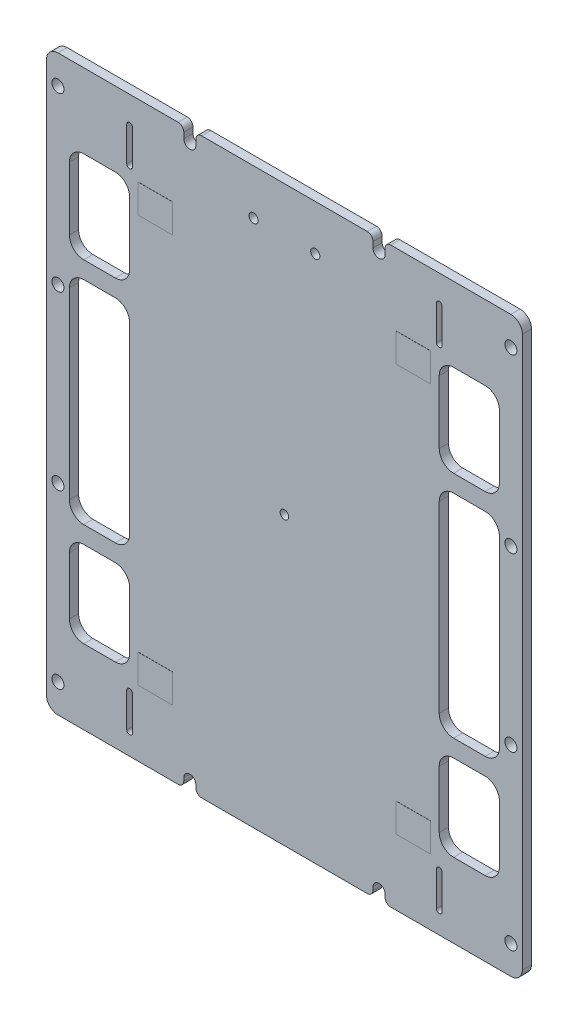
SolidWorks part; units mm, degrees
material "FR4_stuffedProtoboard"
ref_plane "Front Plane" through (0, 0, 0) normal (0, 0, 1) x (1, 0, 0)
ref_plane "Top Plane" through (0, 0, 0) normal (0, 1, 0) x (1, 0, 0)
ref_plane "Right Plane" through (0, 0, 0) normal (1, 0, 0) x (0, 0, -1)
sketch "Sketch1" plane through (0, 0, 0) normal (0, 0, 1) x (1, 0, 0)
  line L1 (-39.5, -50) -> (39.5, -50)
  line L2 (-41.5, -48) -> (-41.5, 48)
  line L3 (-39.5, 50) -> (39.5, 50)
  line L4 (41.5, -48) -> (41.5, 48)
  line L5 (-41.5, -50) -> (41.5, 50) construction
  line L6 (-41.5, 50) -> (41.5, -50) construction
  arc A0 (-39.5, -50) -> (-41.5, -48) centre (-39.5, -48) cw
  arc A1 (39.5, -50) -> (41.5, -48) centre (39.5, -48) ccw
  arc A2 (39.5, 50) -> (41.5, 48) centre (39.5, 48) cw
  arc A3 (-41.5, 48) -> (-39.5, 50) centre (-39.5, 48) cw
  point P0 (0, 0)
  dimension "D3" = 2
  dimension "D1" = 100
  dimension "D2" = 83
extrude "boardOutline" add sketch "Sketch1" along normal blind 1.6
sketch "Sketch2" plane through (0, 0, 1.6) normal (0, 0, 1) x (1, 0, 0)
  line L0 (39.5, 50) -> (-39.5, 50) construction
  line L1 (-41.5, 48) -> (-41.5, -48) construction
  line L2 (-5.385, 42.1) -> (5.385, 42.1) construction
  line L3 (-38, 44.2) -> (-38, 4.2) construction
  line L4 (0, 42.1) -> (0, 50) construction
  circle A0 centre (0, 0) radius 0.75
  circle A1 centre (-38, 44.2) radius 1.05 construction
  circle A2 centre (37.5, 44.2) radius 1.05 construction
  circle A3 centre (37.5, 4.2) radius 1.05 construction
  circle A4 centre (37.5, -35.8) radius 1.05 construction
  circle A5 centre (-38, 4.2) radius 1.05 construction
  circle A6 centre (-38, -35.8) radius 1.05 construction
  circle A7 centre (-5.385, 42.1) radius 0.8
  circle A8 centre (5.385, 42.1) radius 0.8
  dimension "D1" = 1.5
  dimension "D2" = 2.1
  dimension "D9" = 10.77
  dimension "D7" = 1.6
  dimension "D11" = 7.9
  dimension "D3" = 5.8
  dimension "D4" = 3.5
  dimension "D8" = 40
  dimension "D10" = 37.5
  dimension "D5" = 2
  dimension "D6" = 3
extrude "componentHoles" cut sketch "Sketch2" against normal through all
sketch "Sketch4" plane through (0, 0, 1.6) normal (0, 0, 1) x (1, 0, 0)
  line L0 (-27, 39.25) -> (-27, 45.25) construction
  line L1 (-27.5, 39.25) -> (-27.5, 45.25)
  line L2 (-26.5, 39.25) -> (-26.5, 45.25)
  line L3 (39.5, 50) -> (-39.5, 50) construction
  line L4 (-41.5, 48) -> (-41.5, -48) construction
  line L5 (27, 39.25) -> (27, 45.25) construction
  line L6 (26.5, 39.25) -> (26.5, 45.25)
  line L7 (27.5, 39.25) -> (27.5, 45.25)
  line L8 (27, -46.25) -> (27, -40.25) construction
  line L9 (26.5, -46.25) -> (26.5, -40.25)
  line L10 (27.5, -46.25) -> (27.5, -40.25)
  line L11 (-27, -46.25) -> (-27, -40.25) construction
  line L12 (-27.5, -46.25) -> (-27.5, -40.25)
  line L13 (-26.5, -46.25) -> (-26.5, -40.25)
  line L14 (-27, 39.25) -> (27, 39.25) construction
  line L15 (0, 39.25) -> (0, 50) construction
  arc A0 (-27.5, 39.25) -> (-26.5, 39.25) centre (-27, 39.25) ccw
  arc A1 (-26.5, 45.25) -> (-27.5, 45.25) centre (-27, 45.25) ccw
  arc A2 (26.5, 39.25) -> (27.5, 39.25) centre (27, 39.25) ccw
  arc A3 (27.5, 45.25) -> (26.5, 45.25) centre (27, 45.25) ccw
  arc A4 (26.5, -46.25) -> (27.5, -46.25) centre (27, -46.25) ccw
  arc A5 (27.5, -40.25) -> (26.5, -40.25) centre (27, -40.25) ccw
  arc A6 (-27.5, -46.25) -> (-26.5, -46.25) centre (-27, -46.25) ccw
  arc A7 (-26.5, -40.25) -> (-27.5, -40.25) centre (-27, -40.25) ccw
  point P2 (-27, 42.25)
  point P16 (27, 42.25)
  point P23 (27, -43.25)
  point P30 (-27, -43.25)
  dimension "D1" = 4.75
  dimension "D2" = 14
  dimension "D3" = 1
  dimension "D4" = 6
  dimension "D7" = 54
  dimension "D9" = 79.5
  dimension "D5" = 2
  dimension "D6" = 2
extrude "solarCellContactHoles" cut sketch "Sketch4" against normal blind 1.6
sketch "FrameLattice" plane through (0, 0, 0) normal (0, 0, 1) x (1, 0, 0)
  line L4 (-12.5, -19) -> (12.5, -19)
  line L5 (15, -16.5) -> (15, 15.5)
  line L6 (12.5, 18) -> (-12.5, 18)
  line L7 (-15, 15.5) -> (-15, -16.5)
  line L8 (-12.5, -19) -> (12.5, -19)
  line L9 (15, -16.5) -> (15, 15.5)
  line L10 (12.5, 18) -> (-12.5, 18)
  line L11 (-15, 15.5) -> (-15, -16.5)
  line L12 (-12.5, -92) -> (12.5, -92)
  line L13 (15, -89.5) -> (15, -69.5)
  line L14 (12.5, -67) -> (-12.5, -67)
  line L15 (-15, -69.5) -> (-15, -89.5)
  line L16 (-12.5, -92) -> (12.5, -92)
  line L17 (15, -89.5) -> (15, -69.5)
  line L18 (12.5, -67) -> (-12.5, -67)
  line L19 (-15, -69.5) -> (-15, -89.5)
  line L20 (-35, -132) -> (-20.5, -132)
  line L21 (-18, -129.5) -> (-18, -97.5)
  line L22 (-20.5, -95) -> (-35, -95)
  line L23 (-37.5, -97.5) -> (-37.5, -129.5)
  line L24 (-35, -132) -> (-20.5, -132)
  line L25 (-18, -129.5) -> (-18, -97.5)
  line L26 (-20.5, -95) -> (-35, -95)
  line L27 (-37.5, -97.5) -> (-37.5, -129.5)
  line L28 (20.5, -160) -> (35, -160)
  line L29 (37.5, -157.5) -> (37.5, -137.5)
  line L30 (35, -135) -> (20.5, -135)
  line L31 (18, -137.5) -> (18, -157.5)
  line L32 (20.5, -160) -> (35, -160)
  line L33 (37.5, -157.5) -> (37.5, -137.5)
  line L34 (35, -135) -> (20.5, -135)
  line L35 (18, -137.5) -> (18, -157.5)
  line L36 (20.5, -92) -> (35, -92)
  line L37 (37.5, -89.5) -> (37.5, -69.5)
  line L38 (35, -67) -> (20.5, -67)
  line L39 (18, -69.5) -> (18, -89.5)
  line L40 (20.5, -92) -> (35, -92)
  line L41 (37.5, -89.5) -> (37.5, -69.5)
  line L42 (35, -67) -> (20.5, -67)
  line L43 (18, -69.5) -> (18, -89.5)
  line L44 (-35, -92) -> (-20.5, -92)
  line L45 (-18, -89.5) -> (-18, -69.5)
  line L46 (-20.5, -67) -> (-35, -67)
  line L47 (-37.5, -69.5) -> (-37.5, -89.5)
  line L48 (-35, -92) -> (-20.5, -92)
  line L49 (-18, -89.5) -> (-18, -69.5)
  line L50 (-20.5, -67) -> (-35, -67)
  line L51 (-37.5, -69.5) -> (-37.5, -89.5)
  line L52 (20.5, -132) -> (35, -132)
  line L53 (37.5, -129.5) -> (37.5, -97.5)
  line L54 (35, -95) -> (20.5, -95)
  line L55 (18, -97.5) -> (18, -129.5)
  line L56 (20.5, -132) -> (35, -132)
  line L57 (37.5, -129.5) -> (37.5, -97.5)
  line L58 (35, -95) -> (20.5, -95)
  line L59 (18, -97.5) -> (18, -129.5)
  line L60 (-12.5, -160) -> (12.5, -160)
  line L61 (15, -157.5) -> (15, -137.5)
  line L62 (12.5, -135) -> (-12.5, -135)
  line L63 (-15, -137.5) -> (-15, -157.5)
  line L65 (15, -157.5) -> (15, -137.5)
  line L66 (12.5, -135) -> (-12.5, -135)
  line L67 (-15, -137.5) -> (-15, -157.5)
  line L68 (-26.75, -61.5) -> (-26.75, -52.5)
  line L69 (-29.25, -50) -> (-34.5, -50)
  line L70 (-37, -52.5) -> (-37, -61.5)
  line L71 (-34.5, -64) -> (-29.25, -64)
  line L72 (-26.75, -61.5) -> (-26.75, -52.5)
  line L73 (-29.25, -50) -> (-34.5, -50)
  line L74 (-37, -52.5) -> (-37, -61.5)
  line L75 (-34.5, -64) -> (-29.25, -64)
  line L76 (-35, -160) -> (-20.5, -160)
  line L77 (-18, -157.5) -> (-18, -137.5)
  line L78 (-20.5, -135) -> (-35, -135)
  line L79 (-37.5, -137.5) -> (-37.5, -157.5)
  line L80 (-35, -160) -> (-20.5, -160)
  line L81 (-18, -157.5) -> (-18, -137.5)
  line L82 (-20.5, -135) -> (-35, -135)
  line L83 (-37.5, -137.5) -> (-37.5, -157.5)
  line L84 (-12.5, -132) -> (12.5, -132)
  line L85 (15, -129.5) -> (15, -97.5)
  line L86 (12.5, -95) -> (-12.5, -95)
  line L87 (-15, -97.5) -> (-15, -129.5)
  line L88 (-12.5, -132) -> (12.5, -132)
  line L89 (15, -129.5) -> (15, -97.5)
  line L90 (12.5, -95) -> (-12.5, -95)
  line L91 (-15, -97.5) -> (-15, -129.5)
  line L92 (-35, -19) -> (-20.5, -19)
  line L93 (-18, -16.5) -> (-18, 15.5)
  line L94 (-20.5, 18) -> (-35, 18)
  line L95 (-37.5, 15.5) -> (-37.5, -16.5)
  line L96 (-35, -19) -> (-20.5, -19)
  line L97 (-18, -16.5) -> (-18, 15.5)
  line L98 (-20.5, 18) -> (-35, 18)
  line L99 (-37.5, 15.5) -> (-37.5, -16.5)
  line L100 (20.5, -47) -> (35, -47)
  line L101 (37.5, -44.5) -> (37.5, -24.5)
  line L102 (35, -22) -> (20.5, -22)
  line L103 (18, -24.5) -> (18, -44.5)
  line L104 (20.5, -47) -> (35, -47)
  line L105 (37.5, -44.5) -> (37.5, -24.5)
  line L106 (35, -22) -> (20.5, -22)
  line L107 (18, -24.5) -> (18, -44.5)
  line L108 (-12.5, -47) -> (12.5, -47)
  line L109 (15, -44.5) -> (15, -24.5)
  line L110 (12.5, -22) -> (-12.5, -22)
  line L111 (-15, -24.5) -> (-15, -44.5)
  line L112 (-12.5, -47) -> (12.5, -47)
  line L113 (15, -44.5) -> (15, -24.5)
  line L114 (12.5, -22) -> (-12.5, -22)
  line L115 (-15, -24.5) -> (-15, -44.5)
  line L116 (-35, -47) -> (-20.5, -47)
  line L117 (-18, -44.5) -> (-18, -24.5)
  line L118 (-20.5, -22) -> (-35, -22)
  line L119 (-37.5, -24.5) -> (-37.5, -44.5)
  line L120 (-35, -47) -> (-20.5, -47)
  line L121 (-18, -44.5) -> (-18, -24.5)
  line L122 (-20.5, -22) -> (-35, -22)
  line L123 (-37.5, -24.5) -> (-37.5, -44.5)
  line L124 (20.5, -19) -> (35, -19)
  line L125 (37.5, -16.5) -> (37.5, 15.5)
  line L126 (35, 18) -> (20.5, 18)
  line L127 (18, 15.5) -> (18, -16.5)
  line L128 (20.5, -19) -> (35, -19)
  line L129 (37.5, -16.5) -> (37.5, 15.5)
  line L130 (35, 18) -> (20.5, 18)
  line L131 (18, 15.5) -> (18, -16.5)
  line L132 (-35, 21) -> (-20.5, 21)
  line L133 (-18, 23.5) -> (-18, 43.5)
  line L134 (-20.5, 46) -> (-35, 46)
  line L135 (-37.5, 43.5) -> (-37.5, 23.5)
  line L136 (-35, 21) -> (-20.5, 21)
  line L137 (-18, 23.5) -> (-18, 43.5)
  line L138 (-20.5, 46) -> (-35, 46)
  line L139 (-37.5, 43.5) -> (-37.5, 23.5)
  line L140 (-12.5, 21) -> (12.5, 21)
  line L141 (15, 23.5) -> (15, 43.5)
  line L142 (12.5, 46) -> (-12.5, 46)
  line L143 (-15, 43.5) -> (-15, 23.5)
  line L144 (-12.5, 21) -> (12.5, 21)
  line L145 (15, 23.5) -> (15, 43.5)
  line L147 (-15, 43.5) -> (-15, 23.5)
  line L148 (20.5, 21) -> (35, 21)
  line L149 (37.5, 23.5) -> (37.5, 43.5)
  line L150 (35, 46) -> (20.5, 46)
  line L151 (18, 43.5) -> (18, 23.5)
  line L152 (20.5, 21) -> (35, 21)
  line L153 (37.5, 23.5) -> (37.5, 43.5)
  line L154 (35, 46) -> (20.5, 46)
  line L155 (18, 43.5) -> (18, 23.5)
  line L156 (-3.5, -61.5) -> (-3.5, -52.5)
  line L157 (-6, -50) -> (-12.5, -50)
  line L158 (-15, -52.5) -> (-15, -61.5)
  line L159 (-12.5, -64) -> (-6, -64)
  line L160 (-3.5, -61.5) -> (-3.5, -52.5)
  line L161 (-6, -50) -> (-12.5, -50)
  line L162 (-15, -52.5) -> (-15, -61.5)
  line L163 (-12.5, -64) -> (-6, -64)
  line L164 (29.25, -64) -> (34.5, -64)
  line L165 (37, -61.5) -> (37, -52.5)
  line L166 (34.5, -50) -> (29.25, -50)
  line L167 (26.75, -52.5) -> (26.75, -61.5)
  line L168 (29.25, -64) -> (34.5, -64)
  line L169 (37, -61.5) -> (37, -52.5)
  line L170 (34.5, -50) -> (29.25, -50)
  line L171 (26.75, -52.5) -> (26.75, -61.5)
  line L172 (6, -64) -> (12.5, -64)
  line L173 (15, -61.5) -> (15, -52.5)
  line L174 (12.5, -50) -> (6, -50)
  line L175 (3.5, -52.5) -> (3.5, -61.5)
  line L176 (6, -64) -> (12.5, -64)
  line L177 (15, -61.5) -> (15, -52.5)
  line L178 (12.5, -50) -> (6, -50)
  line L179 (3.5, -52.5) -> (3.5, -61.5)
  line L212 (-12.5, -160) -> (12.5, -160)
  line L213 (12.5, 46) -> (-12.5, 46)
  circle A2 centre (-16.5, 48) radius 0.8
  circle A3 centre (-16.5, 48) radius 0.8
  circle A4 centre (-16.5, -162) radius 0.8
  arc A5 (12.5, -19) -> (15, -16.5) centre (12.5, -16.5) ccw
  arc A6 (15, 15.5) -> (12.5, 18) centre (12.5, 15.5) ccw
  arc A7 (-12.5, 18) -> (-15, 15.5) centre (-12.5, 15.5) ccw
  arc A8 (-15, -16.5) -> (-12.5, -19) centre (-12.5, -16.5) ccw
  arc A9 (12.5, -19) -> (15, -16.5) centre (12.5, -16.5) ccw
  arc A10 (15, 15.5) -> (12.5, 18) centre (12.5, 15.5) ccw
  arc A11 (-12.5, 18) -> (-15, 15.5) centre (-12.5, 15.5) ccw
  arc A12 (-15, -16.5) -> (-12.5, -19) centre (-12.5, -16.5) ccw
  arc A13 (12.5, -92) -> (15, -89.5) centre (12.5, -89.5) ccw
  arc A14 (15, -69.5) -> (12.5, -67) centre (12.5, -69.5) ccw
  arc A15 (-12.5, -67) -> (-15, -69.5) centre (-12.5, -69.5) ccw
  arc A16 (-15, -89.5) -> (-12.5, -92) centre (-12.5, -89.5) ccw
  arc A17 (12.5, -92) -> (15, -89.5) centre (12.5, -89.5) ccw
  arc A18 (15, -69.5) -> (12.5, -67) centre (12.5, -69.5) ccw
  arc A19 (-12.5, -67) -> (-15, -69.5) centre (-12.5, -69.5) ccw
  arc A20 (-15, -89.5) -> (-12.5, -92) centre (-12.5, -89.5) ccw
  arc A21 (-20.5, -132) -> (-18, -129.5) centre (-20.5, -129.5) ccw
  arc A22 (-18, -97.5) -> (-20.5, -95) centre (-20.5, -97.5) ccw
  arc A23 (-35, -95) -> (-37.5, -97.5) centre (-35, -97.5) ccw
  arc A24 (-37.5, -129.5) -> (-35, -132) centre (-35, -129.5) ccw
  arc A25 (-20.5, -132) -> (-18, -129.5) centre (-20.5, -129.5) ccw
  arc A26 (-18, -97.5) -> (-20.5, -95) centre (-20.5, -97.5) ccw
  arc A27 (-35, -95) -> (-37.5, -97.5) centre (-35, -97.5) ccw
  arc A28 (-37.5, -129.5) -> (-35, -132) centre (-35, -129.5) ccw
  arc A29 (35, -160) -> (37.5, -157.5) centre (35, -157.5) ccw
  arc A30 (37.5, -137.5) -> (35, -135) centre (35, -137.5) ccw
  arc A31 (20.5, -135) -> (18, -137.5) centre (20.5, -137.5) ccw
  arc A32 (18, -157.5) -> (20.5, -160) centre (20.5, -157.5) ccw
  arc A33 (35, -160) -> (37.5, -157.5) centre (35, -157.5) ccw
  arc A34 (37.5, -137.5) -> (35, -135) centre (35, -137.5) ccw
  arc A35 (20.5, -135) -> (18, -137.5) centre (20.5, -137.5) ccw
  arc A36 (18, -157.5) -> (20.5, -160) centre (20.5, -157.5) ccw
  arc A37 (35, -92) -> (37.5, -89.5) centre (35, -89.5) ccw
  arc A38 (37.5, -69.5) -> (35, -67) centre (35, -69.5) ccw
  arc A39 (20.5, -67) -> (18, -69.5) centre (20.5, -69.5) ccw
  arc A40 (18, -89.5) -> (20.5, -92) centre (20.5, -89.5) ccw
  arc A41 (35, -92) -> (37.5, -89.5) centre (35, -89.5) ccw
  arc A42 (37.5, -69.5) -> (35, -67) centre (35, -69.5) ccw
  arc A43 (20.5, -67) -> (18, -69.5) centre (20.5, -69.5) ccw
  arc A44 (18, -89.5) -> (20.5, -92) centre (20.5, -89.5) ccw
  arc A45 (-20.5, -92) -> (-18, -89.5) centre (-20.5, -89.5) ccw
  arc A46 (-18, -69.5) -> (-20.5, -67) centre (-20.5, -69.5) ccw
  arc A47 (-35, -67) -> (-37.5, -69.5) centre (-35, -69.5) ccw
  arc A48 (-37.5, -89.5) -> (-35, -92) centre (-35, -89.5) ccw
  arc A49 (-20.5, -92) -> (-18, -89.5) centre (-20.5, -89.5) ccw
  arc A50 (-18, -69.5) -> (-20.5, -67) centre (-20.5, -69.5) ccw
  arc A51 (-35, -67) -> (-37.5, -69.5) centre (-35, -69.5) ccw
  arc A52 (-37.5, -89.5) -> (-35, -92) centre (-35, -89.5) ccw
  arc A53 (35, -132) -> (37.5, -129.5) centre (35, -129.5) ccw
  arc A54 (37.5, -97.5) -> (35, -95) centre (35, -97.5) ccw
  arc A55 (20.5, -95) -> (18, -97.5) centre (20.5, -97.5) ccw
  arc A56 (18, -129.5) -> (20.5, -132) centre (20.5, -129.5) ccw
  arc A57 (35, -132) -> (37.5, -129.5) centre (35, -129.5) ccw
  arc A58 (37.5, -97.5) -> (35, -95) centre (35, -97.5) ccw
  arc A59 (20.5, -95) -> (18, -97.5) centre (20.5, -97.5) ccw
  arc A60 (18, -129.5) -> (20.5, -132) centre (20.5, -129.5) ccw
  arc A61 (12.5, -160) -> (15, -157.5) centre (12.5, -157.5) ccw
  arc A62 (15, -137.5) -> (12.5, -135) centre (12.5, -137.5) ccw
  arc A63 (-12.5, -135) -> (-15, -137.5) centre (-12.5, -137.5) ccw
  arc A64 (-15, -157.5) -> (-12.5, -160) centre (-12.5, -157.5) ccw
  arc A65 (12.5, -160) -> (15, -157.5) centre (12.5, -157.5) ccw
  arc A66 (15, -137.5) -> (12.5, -135) centre (12.5, -137.5) ccw
  arc A67 (-12.5, -135) -> (-15, -137.5) centre (-12.5, -137.5) ccw
  arc A68 (-15, -157.5) -> (-12.5, -160) centre (-12.5, -157.5) ccw
  circle A69 centre (-16.5, -162) radius 0.8
  circle A70 centre (16.5, -162) radius 0.8
  circle A71 centre (16.5, -162) radius 0.8
  circle A72 centre (-16.5, -65.5) radius 0.8
  circle A73 centre (-16.5, -65.5) radius 0.8
  circle A74 centre (16.5, -65.5) radius 0.8
  circle A75 centre (16.5, -65.5) radius 0.8
  circle A76 centre (-39.5, -129) radius 0.8
  circle A77 centre (-39.5, -129) radius 0.8
  circle A78 centre (39.5, -159) radius 0.8
  circle A79 centre (39.5, -159) radius 0.8
  circle A80 centre (-39.5, -159) radius 0.8
  circle A81 centre (-39.5, -159) radius 0.8
  circle A82 centre (39.5, -129) radius 0.8
  circle A83 centre (39.5, -129) radius 0.8
  circle A84 centre (39.5, -99) radius 0.8
  circle A85 centre (39.5, -99) radius 0.8
  circle A86 centre (-39.5, -99) radius 0.8
  circle A87 centre (-39.5, -99) radius 0.8
  circle A88 centre (-39.5, -69) radius 0.8
  circle A89 centre (-39.5, -69) radius 0.8
  circle A90 centre (39.5, -69) radius 0.8
  circle A91 centre (39.5, -69) radius 0.8
  circle A92 centre (39.5, -15) radius 0.8
  circle A93 centre (39.5, -15) radius 0.8
  circle A94 centre (39.5, 15) radius 0.8
  arc A95 (-26.75, -52.5) -> (-29.25, -50) centre (-29.25, -52.5) ccw
  arc A96 (-34.5, -50) -> (-37, -52.5) centre (-34.5, -52.5) ccw
  arc A97 (-37, -61.5) -> (-34.5, -64) centre (-34.5, -61.5) ccw
  arc A98 (-29.25, -64) -> (-26.75, -61.5) centre (-29.25, -61.5) ccw
  arc A99 (-26.75, -52.5) -> (-29.25, -50) centre (-29.25, -52.5) ccw
  arc A100 (-34.5, -50) -> (-37, -52.5) centre (-34.5, -52.5) ccw
  arc A101 (-37, -61.5) -> (-34.5, -64) centre (-34.5, -61.5) ccw
  arc A102 (-29.25, -64) -> (-26.75, -61.5) centre (-29.25, -61.5) ccw
  arc A103 (-20.5, -160) -> (-18, -157.5) centre (-20.5, -157.5) ccw
  arc A104 (-18, -137.5) -> (-20.5, -135) centre (-20.5, -137.5) ccw
  arc A105 (-35, -135) -> (-37.5, -137.5) centre (-35, -137.5) ccw
  arc A106 (-37.5, -157.5) -> (-35, -160) centre (-35, -157.5) ccw
  arc A107 (-20.5, -160) -> (-18, -157.5) centre (-20.5, -157.5) ccw
  arc A108 (-18, -137.5) -> (-20.5, -135) centre (-20.5, -137.5) ccw
  arc A109 (-35, -135) -> (-37.5, -137.5) centre (-35, -137.5) ccw
  arc A110 (-37.5, -157.5) -> (-35, -160) centre (-35, -157.5) ccw
  arc A111 (12.5, -132) -> (15, -129.5) centre (12.5, -129.5) ccw
  arc A112 (15, -97.5) -> (12.5, -95) centre (12.5, -97.5) ccw
  arc A113 (-12.5, -95) -> (-15, -97.5) centre (-12.5, -97.5) ccw
  arc A114 (-15, -129.5) -> (-12.5, -132) centre (-12.5, -129.5) ccw
  arc A115 (12.5, -132) -> (15, -129.5) centre (12.5, -129.5) ccw
  arc A116 (15, -97.5) -> (12.5, -95) centre (12.5, -97.5) ccw
  arc A117 (-12.5, -95) -> (-15, -97.5) centre (-12.5, -97.5) ccw
  arc A118 (-15, -129.5) -> (-12.5, -132) centre (-12.5, -129.5) ccw
  arc A119 (-20.5, -19) -> (-18, -16.5) centre (-20.5, -16.5) ccw
  arc A120 (-18, 15.5) -> (-20.5, 18) centre (-20.5, 15.5) ccw
  arc A121 (-35, 18) -> (-37.5, 15.5) centre (-35, 15.5) ccw
  arc A122 (-37.5, -16.5) -> (-35, -19) centre (-35, -16.5) ccw
  arc A123 (-20.5, -19) -> (-18, -16.5) centre (-20.5, -16.5) ccw
  arc A124 (-18, 15.5) -> (-20.5, 18) centre (-20.5, 15.5) ccw
  arc A125 (-35, 18) -> (-37.5, 15.5) centre (-35, 15.5) ccw
  arc A126 (-37.5, -16.5) -> (-35, -19) centre (-35, -16.5) ccw
  arc A127 (35, -47) -> (37.5, -44.5) centre (35, -44.5) ccw
  arc A128 (37.5, -24.5) -> (35, -22) centre (35, -24.5) ccw
  arc A129 (20.5, -22) -> (18, -24.5) centre (20.5, -24.5) ccw
  arc A130 (18, -44.5) -> (20.5, -47) centre (20.5, -44.5) ccw
  arc A131 (35, -47) -> (37.5, -44.5) centre (35, -44.5) ccw
  arc A132 (37.5, -24.5) -> (35, -22) centre (35, -24.5) ccw
  arc A133 (20.5, -22) -> (18, -24.5) centre (20.5, -24.5) ccw
  arc A134 (18, -44.5) -> (20.5, -47) centre (20.5, -44.5) ccw
  arc A135 (12.5, -47) -> (15, -44.5) centre (12.5, -44.5) ccw
  arc A136 (15, -24.5) -> (12.5, -22) centre (12.5, -24.5) ccw
  arc A137 (-12.5, -22) -> (-15, -24.5) centre (-12.5, -24.5) ccw
  arc A138 (-15, -44.5) -> (-12.5, -47) centre (-12.5, -44.5) ccw
  arc A139 (12.5, -47) -> (15, -44.5) centre (12.5, -44.5) ccw
  arc A140 (15, -24.5) -> (12.5, -22) centre (12.5, -24.5) ccw
  arc A141 (-12.5, -22) -> (-15, -24.5) centre (-12.5, -24.5) ccw
  arc A142 (-15, -44.5) -> (-12.5, -47) centre (-12.5, -44.5) ccw
  arc A143 (-20.5, -47) -> (-18, -44.5) centre (-20.5, -44.5) ccw
  arc A144 (-18, -24.5) -> (-20.5, -22) centre (-20.5, -24.5) ccw
  arc A145 (-35, -22) -> (-37.5, -24.5) centre (-35, -24.5) ccw
  arc A146 (-37.5, -44.5) -> (-35, -47) centre (-35, -44.5) ccw
  arc A147 (-20.5, -47) -> (-18, -44.5) centre (-20.5, -44.5) ccw
  arc A148 (-18, -24.5) -> (-20.5, -22) centre (-20.5, -24.5) ccw
  arc A149 (-35, -22) -> (-37.5, -24.5) centre (-35, -24.5) ccw
  arc A150 (-37.5, -44.5) -> (-35, -47) centre (-35, -44.5) ccw
  arc A151 (35, -19) -> (37.5, -16.5) centre (35, -16.5) ccw
  arc A152 (37.5, 15.5) -> (35, 18) centre (35, 15.5) ccw
  arc A153 (20.5, 18) -> (18, 15.5) centre (20.5, 15.5) ccw
  arc A154 (18, -16.5) -> (20.5, -19) centre (20.5, -16.5) ccw
  arc A155 (35, -19) -> (37.5, -16.5) centre (35, -16.5) ccw
  arc A156 (37.5, 15.5) -> (35, 18) centre (35, 15.5) ccw
  arc A157 (20.5, 18) -> (18, 15.5) centre (20.5, 15.5) ccw
  arc A158 (18, -16.5) -> (20.5, -19) centre (20.5, -16.5) ccw
  arc A159 (-20.5, 21) -> (-18, 23.5) centre (-20.5, 23.5) ccw
  arc A160 (-18, 43.5) -> (-20.5, 46) centre (-20.5, 43.5) ccw
  arc A161 (-35, 46) -> (-37.5, 43.5) centre (-35, 43.5) ccw
  arc A162 (-37.5, 23.5) -> (-35, 21) centre (-35, 23.5) ccw
  arc A163 (-20.5, 21) -> (-18, 23.5) centre (-20.5, 23.5) ccw
  arc A164 (-18, 43.5) -> (-20.5, 46) centre (-20.5, 43.5) ccw
  arc A165 (-35, 46) -> (-37.5, 43.5) centre (-35, 43.5) ccw
  arc A166 (-37.5, 23.5) -> (-35, 21) centre (-35, 23.5) ccw
  arc A167 (12.5, 21) -> (15, 23.5) centre (12.5, 23.5) ccw
  arc A168 (15, 43.5) -> (12.5, 46) centre (12.5, 43.5) ccw
  arc A169 (-12.5, 46) -> (-15, 43.5) centre (-12.5, 43.5) ccw
  arc A170 (-15, 23.5) -> (-12.5, 21) centre (-12.5, 23.5) ccw
  arc A171 (12.5, 21) -> (15, 23.5) centre (12.5, 23.5) ccw
  arc A172 (15, 43.5) -> (12.5, 46) centre (12.5, 43.5) ccw
  arc A173 (-12.5, 46) -> (-15, 43.5) centre (-12.5, 43.5) ccw
  arc A174 (-15, 23.5) -> (-12.5, 21) centre (-12.5, 23.5) ccw
  arc A175 (35, 21) -> (37.5, 23.5) centre (35, 23.5) ccw
  arc A176 (37.5, 43.5) -> (35, 46) centre (35, 43.5) ccw
  arc A177 (20.5, 46) -> (18, 43.5) centre (20.5, 43.5) ccw
  arc A178 (18, 23.5) -> (20.5, 21) centre (20.5, 23.5) ccw
  arc A179 (35, 21) -> (37.5, 23.5) centre (35, 23.5) ccw
  arc A180 (37.5, 43.5) -> (35, 46) centre (35, 43.5) ccw
  arc A181 (20.5, 46) -> (18, 43.5) centre (20.5, 43.5) ccw
  arc A182 (18, 23.5) -> (20.5, 21) centre (20.5, 23.5) ccw
  circle A183 centre (39.5, 15) radius 0.8
  circle A184 centre (-39.5, 45) radius 0.8
  circle A185 centre (-39.5, 45) radius 0.8
  circle A186 centre (39.5, 45) radius 0.8
  circle A187 centre (39.5, 45) radius 0.8
  circle A188 centre (-39.5, 15) radius 0.8
  circle A189 centre (-39.5, 15) radius 0.8
  circle A190 centre (16.5, -48.5) radius 0.8
  circle A191 centre (16.5, -48.5) radius 0.8
  circle A192 centre (-16.5, -48.5) radius 0.8
  circle A193 centre (-16.5, -48.5) radius 0.8
  circle A194 centre (16.5, 48) radius 0.8
  circle A195 centre (16.5, 48) radius 0.8
  circle A196 centre (-39.5, -15) radius 0.8
  circle A197 centre (-39.5, -15) radius 0.8
  circle A198 centre (-22, -61) radius 2.75
  circle A199 centre (-22, -61) radius 2.75
  circle A200 centre (-22, -53) radius 2.75
  circle A201 centre (-22, -53) radius 2.75
  circle A202 centre (22, -53) radius 2.75
  circle A203 centre (22, -53) radius 2.75
  circle A204 centre (22, -61) radius 2.75
  arc A205 (-3.5, -52.5) -> (-6, -50) centre (-6, -52.5) ccw
  arc A206 (-12.5, -50) -> (-15, -52.5) centre (-12.5, -52.5) ccw
  arc A207 (-15, -61.5) -> (-12.5, -64) centre (-12.5, -61.5) ccw
  arc A208 (-6, -64) -> (-3.5, -61.5) centre (-6, -61.5) ccw
  arc A209 (-3.5, -52.5) -> (-6, -50) centre (-6, -52.5) ccw
  arc A210 (-12.5, -50) -> (-15, -52.5) centre (-12.5, -52.5) ccw
  arc A211 (-15, -61.5) -> (-12.5, -64) centre (-12.5, -61.5) ccw
  arc A212 (-6, -64) -> (-3.5, -61.5) centre (-6, -61.5) ccw
  circle A213 centre (22, -61) radius 2.75
  circle A214 centre (0, -57) radius 2.75
  circle A215 centre (0, -57) radius 2.75
  circle A216 centre (39.5, -45) radius 0.8
  circle A217 centre (39.5, -45) radius 0.8
  circle A218 centre (-39.5, -45) radius 0.8
  arc A219 (34.5, -64) -> (37, -61.5) centre (34.5, -61.5) ccw
  arc A220 (37, -52.5) -> (34.5, -50) centre (34.5, -52.5) ccw
  arc A221 (29.25, -50) -> (26.75, -52.5) centre (29.25, -52.5) ccw
  arc A222 (26.75, -61.5) -> (29.25, -64) centre (29.25, -61.5) ccw
  arc A223 (34.5, -64) -> (37, -61.5) centre (34.5, -61.5) ccw
  arc A224 (37, -52.5) -> (34.5, -50) centre (34.5, -52.5) ccw
  arc A225 (29.25, -50) -> (26.75, -52.5) centre (29.25, -52.5) ccw
  arc A226 (26.75, -61.5) -> (29.25, -64) centre (29.25, -61.5) ccw
  arc A227 (12.5, -64) -> (15, -61.5) centre (12.5, -61.5) ccw
  arc A228 (15, -52.5) -> (12.5, -50) centre (12.5, -52.5) ccw
  arc A229 (6, -50) -> (3.5, -52.5) centre (6, -52.5) ccw
  arc A230 (3.5, -61.5) -> (6, -64) centre (6, -61.5) ccw
  arc A231 (12.5, -64) -> (15, -61.5) centre (12.5, -61.5) ccw
  arc A232 (15, -52.5) -> (12.5, -50) centre (12.5, -52.5) ccw
  arc A233 (6, -50) -> (3.5, -52.5) centre (6, -52.5) ccw
  arc A234 (3.5, -61.5) -> (6, -64) centre (6, -61.5) ccw
  circle A235 centre (-39.5, -45) radius 0.8
  dimension "D1" = 0
  dimension "D2" = 0
  dimension "D3" = 0
  dimension "D4" = 0
  dimension "D5" = 0
  dimension "D6" = 0
  dimension "D7" = 0
  dimension "D8" = 0
  dimension "D9" = 0
  dimension "D10" = 0
  dimension "D11" = 0
  dimension "D12" = 0
  dimension "D13" = 0
  dimension "D14" = 0
  dimension "D15" = 0
  dimension "D16" = 0
  dimension "D17" = 0
  dimension "D18" = 0
  dimension "D19" = 0
  dimension "D20" = 0
  dimension "D21" = 0
  dimension "D22" = 0
  dimension "D23" = 0
  dimension "D24" = 0
  dimension "D25" = 0
  dimension "D26" = 0
  dimension "D27" = 0
  dimension "D28" = 0
  dimension "D29" = 0
  dimension "D30" = 0
  dimension "D31" = 0
  dimension "D32" = 0
  dimension "D33" = 0
  dimension "D34" = 0
  dimension "D35" = 0
  dimension "D36" = 0
  dimension "D37" = 0
  dimension "D38" = 0
  dimension "D39" = 0
  dimension "D40" = 0
  dimension "D41" = 0
  dimension "D42" = 0
  dimension "D43" = 0
  dimension "D44" = 0
  dimension "D45" = 0
  dimension "D46" = 0
  dimension "D47" = 0
  dimension "D48" = 0
  dimension "D49" = 0
  dimension "D50" = 0
  dimension "D51" = 0
sketch "Sketch3" plane through (0, 0, 1.6) normal (0, 0, 1) x (1, 0, 0)
  line L0 (-35, -19) -> (-20.5, -19) construction
  line L1 (-35, 37) -> (-29.5, 37)
  line L2 (-37.5, 34.5) -> (-37.5, 23.5)
  line L3 (-35, 21) -> (-29.5, 21)
  line L4 (-27, 34.5) -> (-27, 23.5)
  line L6 (-29.5, -22) -> (-35, -22)
  line L7 (-37.5, 15.5) -> (-37.5, -16.5) construction
  line L8 (-20.5, -22) -> (-35, -22) construction
  line L9 (0, 50) -> (0, -50) construction
  line L10 (39.5, 50) -> (-39.5, 50) construction
  line L11 (-39.5, -50) -> (39.5, -50) construction
  line L12 (-27, -24.5) -> (-27, -34.5)
  line L13 (-29.5, -37) -> (-35, -37)
  line L14 (-37.5, -24.5) -> (-37.5, -34.5)
  line L15 (-20.5, 18) -> (-35, 18) construction
  line L16 (-35, 21) -> (-20.5, 21) construction
  line L19 (-29.5, -19) -> (-35, -19)
  line L25 (-27, -16.5) -> (-27, 15.5)
  line L26 (-29.5, 18) -> (-35, 18)
  line L27 (-37.5, -16.5) -> (-37.5, 15.5)
  arc A0 (-37.5, 23.5) -> (-35, 21) centre (-35, 23.5) ccw
  arc A1 (-29.5, 21) -> (-27, 23.5) centre (-29.5, 23.5) ccw
  arc A2 (-29.5, 37) -> (-27, 34.5) centre (-29.5, 34.5) cw
  arc A3 (-35, 37) -> (-37.5, 34.5) centre (-35, 34.5) ccw
  arc A4 (-29.5, -19) -> (-27, -16.5) centre (-29.5, -16.5) ccw
  arc A5 (-27, -34.5) -> (-29.5, -37) centre (-29.5, -34.5) cw
  arc A6 (-35, -37) -> (-37.5, -34.5) centre (-35, -34.5) cw
  arc A7 (-35, -22) -> (-37.5, -24.5) centre (-35, -24.5) ccw
  arc A8 (-29.5, -22) -> (-27, -24.5) centre (-29.5, -24.5) cw
  arc A9 (-37.5, 23.5) -> (-35, 21) centre (-35, 23.5) ccw construction
  arc A17 (-35, -19) -> (-37.5, -16.5) centre (-35, -16.5) cw
  arc A18 (-35, 18) -> (-37.5, 15.5) centre (-35, 15.5) ccw
  arc A19 (-27, 15.5) -> (-29.5, 18) centre (-29.5, 15.5) ccw
  point P12 (-27, 21)
  point P15 (-27, 37)
  point P18 (-37.5, 37)
  dimension "D10" = 13
  dimension "D1" = 10.5
  dimension "D3" = 13
extrude "windows_1side" cut sketch "Sketch3" against normal through all
sketch "Sketch5" plane through (0, 0, 1.6) normal (0, 0, 1) x (1, 0, 0)
  line L0 (-41.5, 48) -> (-41.5, -48) construction
  line L1 (-25.5, 37.5) -> (-19.5, 37.5)
  line L2 (-25.5, 37.5) -> (-25.5, 32.5)
  line L3 (-25.5, 32.5) -> (-19.5, 32.5)
  line L4 (-19.5, 37.5) -> (-19.5, 32.5)
  line L5 (0, 37.5) -> (0, 50) construction
  line L6 (19.5, 37.5) -> (19.5, 32.5)
  line L7 (25.5, 37.5) -> (25.5, 32.5)
  line L8 (19.5, 32.5) -> (25.5, 32.5)
  line L9 (19.5, 37.5) -> (25.5, 37.5)
  line L10 (19.5, -33.5) -> (19.5, -38.5)
  line L11 (25.5, -33.5) -> (25.5, -38.5)
  line L12 (19.5, -38.5) -> (25.5, -38.5)
  line L13 (19.5, -33.5) -> (25.5, -33.5)
  line L14 (-25.5, -33.5) -> (-25.5, -38.5)
  line L15 (-19.5, -33.5) -> (-19.5, -38.5)
  line L16 (-25.5, -38.5) -> (-19.5, -38.5)
  line L17 (-25.5, -33.5) -> (-19.5, -33.5)
  line L18 (-19.5, 37.5) -> (19.5, 37.5) construction
  line L19 (-25.5, 37.5) -> (-25.5, -33.5) construction
  line L20 (39.5, 50) -> (-39.5, 50) construction
  arc A0 (-27.5, 39.25) -> (-26.5, 39.25) centre (-27, 39.25) ccw construction
  dimension "D1" = 5
  dimension "D2" = 6
  dimension "D3" = 16
  dimension "D4" = 1.75
  dimension "D7" = 45
  dimension "D8" = 71
  dimension "D5" = 2
  dimension "D6" = 2
extrude "contactPads" add sketch "Sketch5" along normal blind 0.02
hole_wizard "M2 Clearance Hole1" positions "Sketch6" profile "Sketch7" hole size "M2" standard "ANSI Metric" end condition through all
sketch "Sketch6" plane through (0, 0, 0) normal (0, 0, -1) x (-1, 0, 0)
  line L5 (39.5, -50) -> (39.5, -45) construction
  line L6 (39.5, -50) -> (-39.5, -50) construction
  line L7 (39.5, -45) -> (39.5, -15) construction
  line L8 (39.5, -15) -> (39.5, 15) construction
  line L9 (39.5, 15) -> (39.5, 45) construction
  line L10 (39.5, 45) -> (39.5, 50) construction
  line L11 (-39.5, 50) -> (39.5, 50) construction
  line L15 (37.5, -27.0602) -> (41.5, -27.0602) construction
  line L16 (37.5, -24.5) -> (37.5, -34.5) construction
  line L17 (41.5, 48) -> (41.5, -48) construction
  point P0 (39.5, 45)
  point P27 (39.5, -15)
  point P36 (39.5, -45)
  point P38 (39.5, 15)
  point P73 (39.5, -27.0602)
  dimension "D2" = 5
sketch "Sketch7" plane through (-39.5, 45, 0) normal (1, 0, 0) x (0, 1, 0)
  line L0 (0, 0) -> (0, 1.62)
  line L1 (0, 1.62) -> (1.05, 1.62)
  line L2 (1.05, 1.62) -> (1.05, 0)
  line L5 (1.05, 0) -> (0, 0)
  line L11 (0, -6.35) -> (0, 107.95) construction
  dimension "Thru Hole Dia." = 2.1
  dimension "Thru Hole Depth" = 1.62
sketch "Sketch10" plane through (0, 0, 0) normal (0, 0, -1) x (-1, 0, 0)
  line L0 (16.5, 48) -> (16.5, 55.0732) construction
  line L1 (15.45, 48) -> (15.45, 55.0732)
  line L2 (17.55, 48) -> (17.55, 55.0732)
  line L3 (16.5, -48.5) -> (16.5, -55.5732) construction
  line L4 (17.55, -48.5) -> (17.55, -55.5732)
  line L5 (15.45, -48.5) -> (15.45, -55.5732)
  line L6 (41.5, 48) -> (41.5, -48) construction
  line L8 (39.5, -50) -> (-39.5, -50) construction
  line L9 (-39.5, 50) -> (39.5, 50) construction
  arc A0 (15.45, 48) -> (17.55, 48) centre (16.5, 48) ccw
  arc A1 (17.55, 55.0732) -> (15.45, 55.0732) centre (16.5, 55.0732) ccw
  arc A2 (17.55, -48.5) -> (15.45, -48.5) centre (16.5, -48.5) ccw
  arc A3 (15.45, -55.5732) -> (17.55, -55.5732) centre (16.5, -55.5732) ccw
  point P2 (16.5, 51.5366)
  point P7 (16.5, -52.0366)
  dimension "D1" = 1.05
  dimension "D2" = 25
  dimension "D3" = 2
  dimension "D4" = 1.5
extrude "Cut-Extrude1" cut sketch "Sketch10" against normal through all both and the other way through all
fillet "Fillet3" radius 1 4 edges at (-17.55, 50, 0.8) (-15.45, 50, 0.8) (-15.45, -50, 0.8) (-17.55, -50, 0.8)
mirror "Mirror1" about plane through (0, 0, 0) normal (1, 0, 0) of "Cut-Extrude1", "Fillet3", "windows_1side", "M2 Clearance Hole1"
